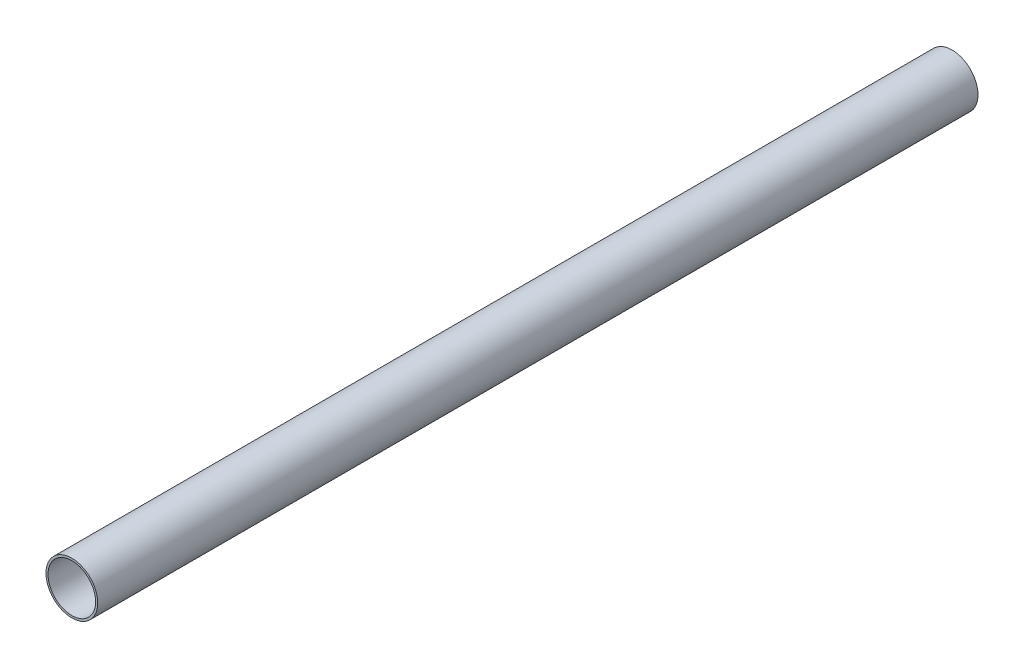
SolidWorks part; units mm, degrees
ref_plane "Спереди" through (0, 0, 0) normal (0, 0, 1) x (1, 0, 0)
ref_plane "Сверху" through (0, 0, 0) normal (0, 1, 0) x (1, 0, 0)
ref_plane "Справа" through (0, 0, 0) normal (1, 0, 0) x (0, 0, -1)
other "Configuration Table"
sketch "Эскиз1" plane through (0, 0, 0) normal (0, 0, 1) x (1, 0, 0)
  circle A0 centre (0, 0) radius 50
  circle A1 centre (0, 0) radius 46
  dimension "D1" = 100
  dimension "D2" = 4
extrude "Бобышка-Вытянуть1" add sketch "Эскиз1" along normal blind 1700
ref_axis "Ось1" through (0, 0, 1700) along (0, 0, -1)
